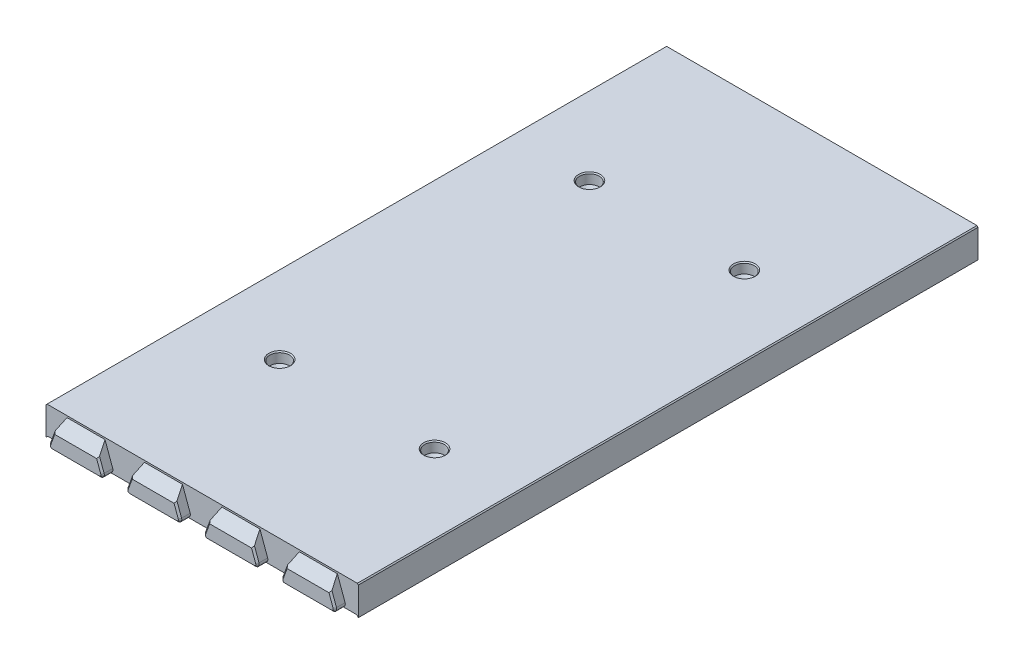
SolidWorks part; units mm, degrees
ref_plane "Front Plane" through (0, 0, 0) normal (0, 0, 1) x (1, 0, 0)
ref_plane "Top Plane" through (0, 0, 0) normal (0, 1, 0) x (1, 0, 0)
ref_plane "Right Plane" through (0, 0, 0) normal (1, 0, 0) x (0, 0, -1)
sketch "Sketch1" plane through (0, 0, 0) normal (0, 0, 1) x (1, 0, 0)
  line L0 (0, 0) -> (0, 8) construction
  line L1 (-45.375, 0) -> (0, 0) construction
  line L2 (-45.375, 0) -> (-45.375, 8)
  line L3 (-45.375, 8) -> (45.375, 8)
  line L5 (-45.375, 0) -> (-43.375, 0)
  line L6 (-43.375, 0) -> (-43.375, 6)
  line L7 (-43.375, 6) -> (43.375, 6)
  line L9 (43.375, 0) -> (43.375, 6)
  line L10 (45.375, 0) -> (43.375, 0)
  line L11 (45.375, 0) -> (45.375, 8)
  point P8 (0, 6)
  dimension "D2" = 6
  dimension "D1" = 45.375
  dimension "D3" = 2
  dimension "D4" = 2
extrude "Boss-Extrude1" add sketch "Sketch1" against normal blind 90
sketch "Sketch7" plane through (0, 0, 0) normal (0, 0, 1) x (1, 0, 0)
  line L2 (-43.375, 0) -> (43.375, 0)
  line L13 (-43.375, 0) -> (-43.375, 6)
  line L15 (-43.375, 6) -> (43.375, 6)
  line L16 (43.375, 0) -> (43.375, 6)
  line M3 (-43.375, 0) -> (-43.375, 6)
  line M4 (-43.375, 6) -> (43.375, 6)
  line M5 (43.375, 6) -> (43.375, 0)
extrude "Boss-Extrude7" add sketch "Sketch7" against normal blind 1 contours M4 M3 | M5 region at (0, 3, 0)
sketch "Sketch2" plane through (0, 0, 0) normal (0, 0, 1) x (1, 0, 0)
  line L14 (28.4118, 8) -> (25.5, 0)
  line L15 (45.375, 8) -> (-45.375, 8) construction
  line L16 (-45.375, 0) -> (45.375, 0) construction
  line L17 (25.5, 0) -> (42, 0)
  line L18 (28.4118, 8) -> (39.0882, 8)
  line L19 (-45.375, 0) -> (45.375, 0) construction
  line L21 (39.0882, 8) -> (42, 0)
  line L24 (22.5, 0) -> (22.5, 8) construction
  line L27 (5.9118, 8) -> (3, 0)
  line L28 (5.9118, 8) -> (16.5882, 8)
  line L29 (3, 0) -> (19.5, 0)
  line L30 (16.5882, 8) -> (19.5, 0)
  line L31 (-16.5882, 8) -> (-19.5, 0)
  line L32 (-16.5882, 8) -> (-5.9118, 8)
  line L33 (-19.5, 0) -> (-3, 0)
  line L34 (-5.9118, 8) -> (-3, 0)
  line L35 (-39.0882, 8) -> (-42, 0)
  line L36 (-39.0882, 8) -> (-28.4118, 8)
  line L37 (-42, 0) -> (-25.5, 0)
  line L38 (-28.4118, 8) -> (-25.5, 0)
  line L39 (28.4118, 8) -> (5.9118, 8) construction
  line L40 (45, 8) -> (45, 0) construction
  line L41 (45.375, 0) -> (45.375, 8) construction
  line L42 (-45, 8) -> (-45, 0) construction
  line L43 (-45.375, 8) -> (-45.375, 0) construction
  point P22 (33.75, 8)
  point P23 (11.25, 8)
  dimension "D1" = 70
  dimension "D2" = 0.375
  dimension "D3" = 3
  dimension "D4" = 3
  dimension "D5" = 70
  dimension "D7" = 22.5
  dimension "D8" = 22.5
  dimension "D9" = 0.375
  dimension "D10" = 3
  dimension "D11" = 8
  dimension "D6" = 4
extrude "Boss-Extrude4" add sketch "Sketch2" along normal blind 3
sketch "Sketch8" plane through (0, 0, 0) normal (0, -1, 0) x (1, 0, 0)
  line L0 (-45.375, -22.5) -> (45.375, -22.5) construction
  line L2 (45.375, -90) -> (45.375, 0) construction
  line L3 (-45.375, 0) -> (-42, 0) construction
  line L4 (-44, -24.9559) -> (-44, -20.0441)
  line L5 (-44, -20.0441) -> (-40, -21.5)
  line L6 (-40, -21.5) -> (-40, -23.5)
  line L7 (-44, -90) -> (-44, -87.5441)
  line L8 (-44, -87.5441) -> (-40, -89)
  line L9 (-40, -89) -> (-40, -90)
  line L10 (-43.375, -90) -> (43.375, -90) construction
  line L11 (-40, -90) -> (-44, -90)
  line L12 (-44, -24.9559) -> (-40, -23.5)
  line L13 (0, -90) -> (0, 0) construction
  line L23 (-45.375, -90) -> (-45.375, 0) construction
  line L24 (44, -24.9559) -> (40, -23.5)
  line L25 (40, -21.5) -> (40, -23.5)
  line L26 (44, -20.0441) -> (40, -21.5)
  line L27 (44, -24.9559) -> (44, -20.0441)
  line L28 (-45.375, -90) -> (-43.375, -90) construction
  line L29 (40, -90) -> (44, -90)
  line L30 (40, -89) -> (40, -90)
  line L31 (44, -87.5441) -> (40, -89)
  line L32 (44, -90) -> (44, -87.5441)
  point P19 (-40, -22.5)
  point P32 (40, -22.5)
  dimension "D1" = 22.5
  dimension "D3" = 70
  dimension "D4" = 4
  dimension "D5" = 1.375
  dimension "D6" = 4
  dimension "D7" = 70
  dimension "D8" = 1
  dimension "D9" = 1
extrude "Boss-Extrude8" add sketch "Sketch8" against normal up to next and the other way blind 2
chamfer "Chamfer4" distance 0.5 angle 45 14 edges at (-40, -2, -89.5) (-42, -2, -88.2721) (-44, -2, -88.7721) (-42, -2, -24.2279) (-40, -2, -22.5) (-42, -2, -20.7721) (40, -2, -22.5) (42, -2, -24.2279) (42, -2, -20.7721) (44, -2, -22.5) (40, -2, -89.5) (44, -2, -88.7721) (42, -2, -88.2721) (-44, -2, -22.5)
fillet "Fillet4" radius 1 8 edges at (42, 0, 1.5) (25.5, 0, 1.5) (19.5, 0, 1.5) (3, 0, 1.5) (-3, 0, 1.5) (-19.5, 0, 1.5) (-25.5, 0, 1.5) (-42, 0, 1.5)
chamfer "Chamfer6" distance 0.5 angle 45 20 edges at (27.2001, 4.671, 3) (40.2999, 4.671, 3) (33.75, 0, 3) (-40.2999, 4.671, 3) (-33.75, 0, 3) (-27.2001, 4.671, 3) (-17.7999, 4.671, 3) (-11.25, 0, 3) (-4.7001, 4.671, 3) (4.7001, 4.671, 3) (17.7999, 4.671, 3) (11.25, 0, 3) (-41.391, 0.4264, 3) (-26.109, 0.4264, 3) (-18.891, 0.4264, 3) (-3.609, 0.4264, 3) (3.609, 0.4264, 3) (18.891, 0.4264, 3) (26.109, 0.4264, 3) (41.391, 0.4264, 3)
fillet "Fillet2" radius 2 23 edges at (0, 6, -1) (-43.375, 3, -87.7716) (-41.6875, 6, -88.3858) (-40, 6, -89.5) (-43.375, 3, -1) (-41.6875, 6, -20.8858) (-43.375, 3, -20.2716) (-43.375, 6, -56.25) (-40, 6, -22.5) (-41.6875, 6, -24.1142) (-43.375, 3, -24.7284) (43.375, 6, -10.6358) (43.375, 3, -1) (-43.375, 6, -10.6358) (43.375, 3, -24.7284) (43.375, 3, -20.2716) (43.375, 3, -87.7716) (40, 6, -89.5) (41.6875, 6, -88.3858) (41.6875, 6, -20.8858) (40, 6, -22.5) (43.375, 6, -56.25) (41.6875, 6, -24.1142)
mirror "Mirror2" about plane through (0, 0, -90) normal (0, 0, 1) of "Fillet4", "Boss-Extrude1", "Boss-Extrude7", "Boss-Extrude4", "Boss-Extrude8", "Chamfer4", "Fillet2", "Chamfer6"
sketch "Sketch9" plane through (0, 0, 0) normal (0, 1, 0) x (1, 0, 0)
  line L0 (-28.5, 39) -> (-16.5, 39) construction
  line L1 (-16.5, 39) -> (-16.5, 51) construction
  line L2 (-16.5, 51) -> (-28.5, 51) construction
  line L3 (-28.5, 51) -> (-28.5, 39) construction
  line L4 (16.5, 39) -> (28.5, 39) construction
  line L5 (28.5, 39) -> (28.5, 51) construction
  line L6 (28.5, 51) -> (16.5, 51) construction
  line L7 (16.5, 51) -> (16.5, 39) construction
  line L8 (16.5, 129) -> (28.5, 129) construction
  line L9 (28.5, 129) -> (28.5, 141) construction
  line L10 (28.5, 141) -> (16.5, 141) construction
  line L11 (16.5, 141) -> (16.5, 129) construction
  line L12 (-28.5, 129) -> (-16.5, 129) construction
  line L13 (-16.5, 129) -> (-16.5, 141) construction
  line L14 (-16.5, 141) -> (-28.5, 141) construction
  line L15 (-28.5, 141) -> (-28.5, 129) construction
  line L16 (-16.5, 129) -> (16.5, 51) construction
  line L17 (-45.375, 90) -> (45.375, 90) construction
  line L18 (-45.375, 92.9563) -> (-45.375, 87.0437) construction
  line L19 (-28.5, 129) -> (-16.5, 141) construction
  line L20 (45.375, 180) -> (45.375, 0) construction
  line L21 (16.5, 129) -> (28.5, 141) construction
  line L22 (-28.5, 39) -> (-16.5, 51) construction
  line L23 (16.5, 39) -> (28.5, 51) construction
  circle A0 centre (-22.5, 45) radius 5
  circle A1 centre (22.5, 45) radius 5
  circle A2 centre (22.5, 135) radius 5
  circle A3 centre (-22.5, 135) radius 5
  point P23 (0, 90)
  point P24 (0, 90)
  dimension "D4" = 10
  dimension "D1" = 12
  dimension "D2" = 78
  dimension "D3" = 33
extrude "Boss-Extrude9" add sketch "Sketch9" along normal up to next
fillet "Fillet3" radius 3 4 edges at (22.5, 6, -50) (-22.5, 6, -50) (-22.5, 6, -140) (22.5, 6, -140)
sketch "Sketch10" plane through (0, 0, 0) normal (0, 1, 0) x (1, 0, 0)
  circle A0 centre (-22.5, 135) radius 1.85
  circle A1 centre (-22.5, 45) radius 1.85
  circle A2 centre (22.5, 45) radius 1.85
  circle A3 centre (22.5, 135) radius 1.85
  circle A4 centre (-22.5, 45) radius 5 construction
  circle A5 centre (22.5, 45) radius 5 construction
  circle A6 centre (22.5, 135) radius 5 construction
  circle A7 centre (-22.5, 135) radius 5 construction
  circle A8 centre (-22.5, 45) radius 5 construction
  circle A9 centre (22.5, 45) radius 5 construction
  circle A10 centre (22.5, 135) radius 5 construction
  circle A11 centre (-22.5, 135) radius 5 construction
  dimension "D1" = 3.7
extrude "Cut-Extrude2" cut sketch "Sketch10" along normal through all
sketch "Sketch11" plane through (0, 8, 0) normal (0, 1, 0) x (1, 0, 0)
  circle A0 centre (-22.5, 135) radius 2.85
  circle A1 centre (22.5, 135) radius 2.85
  circle A2 centre (22.5, 45) radius 2.85
  circle A3 centre (-22.5, 45) radius 2.85
  dimension "D1" = 5.7
extrude "Cut-Extrude3" cut sketch "Sketch11" against normal blind 3
chamfer "Chamfer7" distance 1 angle 45 4 edges at (22.5, 5, -133.15) (-22.5, 5, -133.15) (22.5, 5, -43.15) (-22.5, 5, -43.15)
sketch "Sketch12" plane through (0, 0, 0) normal (1, 0, 0) x (0, 0, -1)
  line L0 (0, 7.5) -> (-3, 4.5)
  line L1 (-3, 1.171) -> (-3, 8) construction
  line L2 (-3, 4.5) -> (-3, 7.5)
  line L3 (-3, 7.5) -> (0, 7.5) construction
  line L4 (90, 8) -> (90, 0) construction
  line L5 (180, 8) -> (0, 8) construction
  line L6 (180, 0) -> (0, 0) construction
  line L8 (183, 4.5) -> (183, 7.5)
  line L9 (180, 7.5) -> (183, 4.5)
  line L10 (0, 0) -> (0, 8) construction
  line L11 (-3, 8) -> (-2.5, 8) construction
  line L12 (-3, 7.5) -> (-3, 8)
  line L13 (-3, 8) -> (0, 8)
  line L14 (0, 8) -> (0, 7.5)
  line L15 (183, 7.5) -> (180, 7.5) construction
  line L16 (180, 8) -> (180, 7.5)
  line L17 (183, 8) -> (180, 8)
  line L18 (183, 7.5) -> (183, 8)
  dimension "D1" = 45
  dimension "D2" = 3
  dimension "D3" = 0.5
extrude "Cut-Extrude4" cut sketch "Sketch12" against normal through all both and the other way through all
sketch "Sketch13" plane through (0, 0, -180) normal (0, 0, -1) x (-1, 0, 0)
  line L0 (-44.875, 0) -> (-45.375, -0.5)
  line L1 (-40.5719, 0) -> (-45.375, 0) construction
  line L2 (-45.375, -0.5) -> (-45.375, 0)
  line L3 (-45.375, 0) -> (-44.875, 0)
  line L4 (0, 0) -> (0, 8) construction
  line L5 (-45.375, 8) -> (45.375, 8) construction
  line L6 (45.375, 0) -> (44.875, 0)
  line L7 (45.375, -0.5) -> (45.375, 0)
  line L8 (44.875, 0) -> (45.375, -0.5)
  dimension "D1" = 0.5
  dimension "D2" = 0.5
extrude "Boss-Extrude10" add sketch "Sketch13" against normal up to surface (180 mm away) up to face at (0, 3.0278, 0)
chamfer "Chamfer8" distance 0.3 angle 45 6 edges at (-45.375, 8, -90) (45.375, 8, -90) (-22.5, 8, -132.15) (22.5, 8, -132.15) (-22.5, 8, -42.15) (22.5, 8, -42.15)
